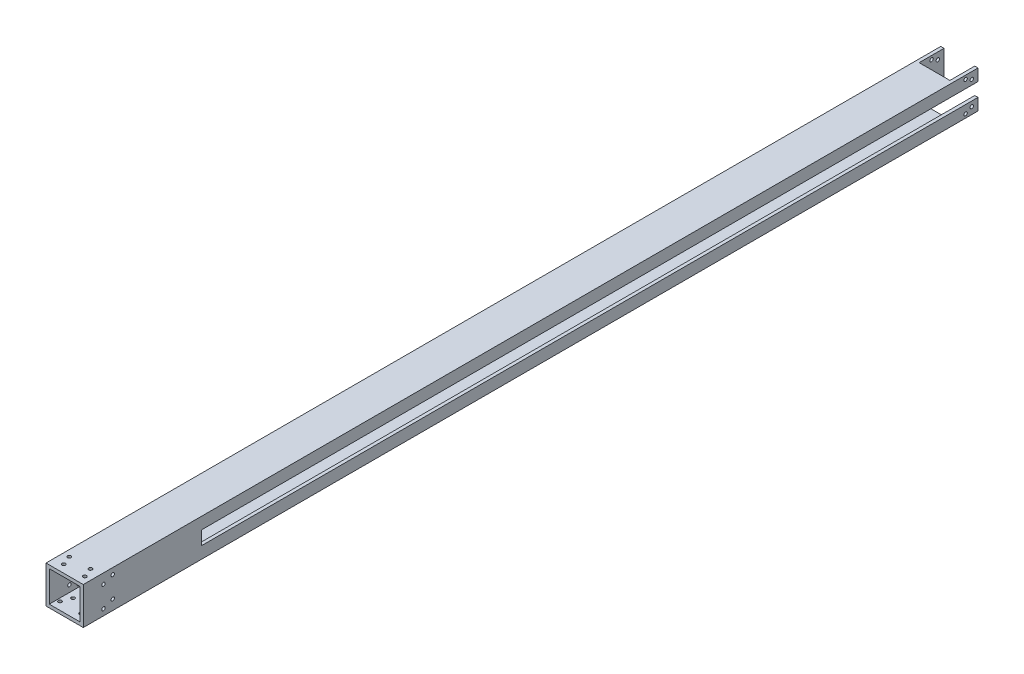
SolidWorks part; units mm, degrees
ref_plane "Front Plane" through (0, 0, 0) normal (1, 0, 0) x (0, 1, 0)
ref_plane "Top Plane" through (0, 0, 0) normal (0, 0, 1) x (0, 1, 0)
ref_plane "Right Plane" through (0, 0, 0) normal (0, 1, 0) x (-1, 0, 0)
sketch "Sketch1" plane through (0, 0, 0) normal (0, 0, 1) x (0, 1, 0)
  line L0 (19.05, -19.05) -> (19.05, 19.05)
  line L1 (19.05, -19.05) -> (-19.05, -19.05)
  line L2 (19.05, -19.05) -> (19.05, 19.05)
  line L3 (19.05, 19.05) -> (-19.05, 19.05)
  line L4 (-19.05, -19.05) -> (-19.05, 19.05)
  line L5 (19.05, -19.05) -> (-19.05, 19.05) construction
  line L6 (19.05, 19.05) -> (-19.05, -19.05) construction
  line L7 (19.05, 19.05) -> (-19.05, 19.05)
  line L8 (-19.05, -19.05) -> (-19.05, 19.05)
  line L9 (19.05, -19.05) -> (-19.05, -19.05)
  line L10 (15.7163, 15.7163) -> (-15.7162, 15.7163)
  line L11 (-15.7162, -15.7163) -> (-15.7162, 15.7163)
  line L12 (15.7163, -15.7162) -> (-15.7162, -15.7163)
  line L13 (15.7163, -15.7162) -> (15.7163, 15.7163)
  line L14 (-6.985, -15.7162) -> (-6.985, -19.05)
  line L15 (6.985, -15.7163) -> (6.985, -19.05)
  line L16 (-15.7162, -15.7163) -> (-6.985, -15.7162)
  line L17 (-6.985, -17.3831) -> (-19.05, -17.3831) construction
  line L18 (6.985, -17.3831) -> (19.05, -17.3831) construction
  point P0 (0, 0)
  dimension "D1" = 38.1
  dimension "D4" = 13.97
  dimension "D3" = 31.4325
  dimension "D2" = 0
extrude "Boss-Extrude1" add sketch "Sketch1" along normal blind 914.4 contours L4 L1 L0 L3 L13 L12 L11 L10 region at (18.5112, 13.0175, 0)
sketch "Sketch6" plane through (0, 0, 0) normal (0, 0, 1) x (0, 1, 0)
  line L1 (26.9875, -26.9875) -> (-26.9875, -26.9875) construction
  line L2 (26.9875, -26.9875) -> (26.9875, 26.9875) construction
  line L3 (26.9875, 26.9875) -> (-26.9875, 26.9875) construction
  line L4 (-26.9875, -26.9875) -> (-26.9875, 26.9875) construction
  line L5 (26.9875, -26.9875) -> (-26.9875, 26.9875) construction
  line L6 (26.9875, 26.9875) -> (-26.9875, -26.9875) construction
  line L11 (-26.9875, 25.8156) -> (-16.9875, 25.8156)
  line L12 (-26.9875, 25.8156) -> (-26.9875, 21.8156)
  line L13 (-26.9875, 21.8156) -> (-16.9875, 21.8156)
  line L14 (-16.9875, 25.8156) -> (-16.9875, 21.8156)
  line L15 (-23.4875, 25.8156) -> (-20.4875, 25.8156)
  line L16 (-23.4875, 25.8156) -> (-23.4875, -2.5726)
  line L17 (-23.4875, -2.5726) -> (-20.4875, -2.5726)
  line L18 (-20.4875, 25.8156) -> (-20.4875, -2.5726)
  point P0 (0, 0)
  point P14 (-21.9875, 25.8156)
  point P15 (-21.9875, 25.8156)
  dimension "D1" = 53.975
  dimension "D2" = 4
  dimension "D3" = 10
  dimension "D4" = 3
sketch "Sketch8" plane through (0, 19.05, 0) normal (0, 1, 0) x (-1, 0, 0)
  line L0 (-19.05, 0) -> (19.05, 0) construction
  line L1 (15.7163, -25.4) -> (-15.7162, -25.4)
  line L2 (15.7163, -25.4) -> (15.7163, 25.4)
  line L3 (15.7163, 25.4) -> (-15.7162, 25.4)
  line L4 (-15.7162, -25.4) -> (-15.7162, 25.4)
  line L5 (15.7163, -25.4) -> (-15.7162, 25.4) construction
  line L6 (15.7163, 25.4) -> (-15.7162, -25.4) construction
  point P0 (0, 0)
  dimension "1.25" = 31.4325
  dimension "D2" = 25.4
extrude "Cut-Extrude3" cut sketch "Sketch8" against normal blind 71.882
ref_axis "Axis1" through (0, 0, 960.12) along (0, 0, -1)
sketch "Sketch11" plane through (19.05, 0, 0) normal (1, 0, 0) x (0, 1, 0)
  line L0 (6.985, 914.4) -> (6.985, 0) construction
  line L1 (-6.985, 0) -> (6.985, 0)
  line L2 (-6.985, 0) -> (-6.985, 12.7)
  line L3 (-6.985, 12.7) -> (6.985, 12.7)
  line L4 (6.985, 0) -> (6.985, 12.7)
  dimension "D1" = 12.7
sketch "Sketch9" plane through (19.05, 0, 0) normal (1, 0, 0) x (0, 1, 0)
  line L0 (19.05, 0) -> (6.985, 0) construction
  line L1 (-6.985, 0) -> (-19.05, 0) construction
  line L2 (19.05, 0) -> (6.985, 0) construction
  line L3 (-6.985, 0) -> (-19.05, 0) construction
  line L4 (15.7163, 25.4) -> (19.05, 25.4) construction
  line L6 (15.7163, 25.4) -> (19.05, 25.4) construction
  line L10 (0, 0) -> (0, 6.35) construction
  circle A0 centre (-15.24, 12.7) radius 1.75
  circle A2 centre (15.24, 12.7) radius 1.75
  circle A3 centre (15.24, 12.7) radius 10.541 construction
  circle A5 centre (12.065, 6.35) radius 1.75
  circle A6 centre (-12.065, 6.35) radius 1.75
  point P12 (4.699, 12.7)
  point P15 (-15.24, 12.7)
  dimension "D2" = 3.5
  dimension "D3" = 6.35
  dimension "D5" = 21.082
  dimension "D7" = 3.175
  dimension "D1" = 0
  dimension "D4" = 15.24
  dimension "D6" = 12.7
  dimension "D8" = 6.35
extrude "Cut-Extrude4" cut sketch "Sketch9" against normal blind 68.326
sketch "Sketch12" plane through (19.05, 0, 0) normal (1, 0, 0) x (0, 1, 0)
  line L0 (19.05, 914.4) -> (19.05, 0) construction
  line L1 (-19.05, 914.4) -> (19.05, 914.4)
  line L2 (-19.05, 914.4) -> (-19.05, 793.75)
  line L3 (-19.05, 793.75) -> (19.05, 793.75)
  line L4 (19.05, 914.4) -> (19.05, 793.75)
  dimension "D1" = 793.75
extrude "Boss-Extrude3" add sketch "Sketch12" against normal up to surface (3.3338 mm away) up to face at (15.7163, 16.99, 12.7)
sketch "Sketch13" plane through (19.05, 0, 0) normal (1, 0, 0) x (0, 1, 0)
  line L0 (-8.89, 884.2375) -> (-12.7, 884.2375) construction
  line L1 (-8.89, 884.2375) -> (-8.89, 893.7625) construction
  line L2 (-8.89, 893.7625) -> (-12.7, 893.7625) construction
  line L3 (-12.7, 884.2375) -> (-12.7, 893.7625) construction
  line L4 (-8.89, 884.2375) -> (-12.7, 893.7625) construction
  line L5 (-8.89, 893.7625) -> (-12.7, 884.2375) construction
  line L6 (-19.05, 914.4) -> (-19.05, 0) construction
  line L7 (19.05, 914.4) -> (-19.05, 914.4) construction
  line L8 (19.05, 914.4) -> (19.05, 0) construction
  line L9 (-15.7162, 914.4) -> (-15.7163, 25.4) construction
  line L10 (-15.7162, 914.4) -> (-15.7163, 25.4) construction
  circle A0 centre (-12.7, 893.7625) radius 1.75
  circle A1 centre (-8.89, 884.2375) radius 1.75
  circle A2 centre (8.89, 893.7625) radius 1.75
  circle A3 centre (12.7, 884.2375) radius 1.75
  circle A4 centre (-12.7, 893.7625) radius 3 construction
  point P0 (-10.795, 889)
  dimension "D1" = 3.5
  dimension "D8" = 6
  dimension "D2" = 6.35
  dimension "D3" = 25.4
  dimension "D4" = 3.81
  dimension "D5" = 9.525
  dimension "D7" = 6.35
  dimension "D6" = 2
extrude "Cut-Extrude5" cut sketch "Sketch13" against normal blind 6.604
pattern_circular "CirPattern1" count 2 over 360 about axis through (0, 0, 960.12) along (0, 0, -1) of "Cut-Extrude5"
sketch "Sketch14" plane through (0, -19.05, 0) normal (0, -1, 0) x (1, 0, 0)
  line L0 (12.7, 896.9375) -> (8.89, 896.9375) construction
  line L1 (12.7, 896.9375) -> (12.7, 906.4625) construction
  line L2 (12.7, 906.4625) -> (8.89, 906.4625) construction
  line L3 (8.89, 896.9375) -> (8.89, 906.4625) construction
  line L4 (12.7, 896.9375) -> (8.89, 906.4625) construction
  line L5 (12.7, 906.4625) -> (8.89, 896.9375) construction
  line L6 (19.05, 914.4) -> (19.05, 0) construction
  line L7 (19.05, 914.4) -> (-19.05, 914.4) construction
  line L8 (0, 914.4) -> (0, 916.8076) construction
  line L9 (-19.05, 914.4) -> (-19.05, 0) construction
  circle A0 centre (8.89, 906.4625) radius 1.75
  circle A1 centre (12.7, 896.9375) radius 1.75
  circle A2 centre (8.89, 906.4625) radius 3 construction
  circle A3 centre (-12.7, 906.4625) radius 1.75
  circle A4 centre (-8.89, 896.9375) radius 1.75
  point P0 (10.795, 901.7)
  dimension "D1" = 3.5
  dimension "D4" = 6
  dimension "D2" = 3.81
  dimension "D3" = 9.525
  dimension "D5" = 6.35
  dimension "D6" = 12.7
  dimension "D8" = 6.35
  dimension "D7" = 2
extrude "Cut-Extrude6" cut sketch "Sketch14" against normal blind 18.796
pattern_circular "CirPattern2" count 2 over 360 about axis through (0, 0, 960.12) along (0, 0, -1) of "Cut-Extrude6"
sketch "Sketch15" plane through (-19.05, 0, 0) normal (-1, 0, 0) x (0, -1, 0)
  line L0 (2.54, 46.0375) -> (-2.54, 46.0375) construction
  line L1 (2.54, 46.0375) -> (2.54, 55.5625) construction
  line L2 (2.54, 55.5625) -> (-2.54, 55.5625) construction
  line L3 (-2.54, 46.0375) -> (-2.54, 55.5625) construction
  line L4 (2.54, 46.0375) -> (-2.54, 55.5625) construction
  line L5 (2.54, 55.5625) -> (-2.54, 46.0375) construction
  line L6 (-19.05, 0) -> (19.05, 0) construction
  circle A0 centre (-2.54, 55.5625) radius 3
  circle A1 centre (2.54, 46.0375) radius 3
  point P0 (0, 50.8)
  dimension "D1" = 6
  dimension "D2" = 9.525
  dimension "D3" = 5.08
  dimension "D4" = 50.8
extrude "Cut-Extrude7" cut sketch "Sketch15" against normal blind 18.796
